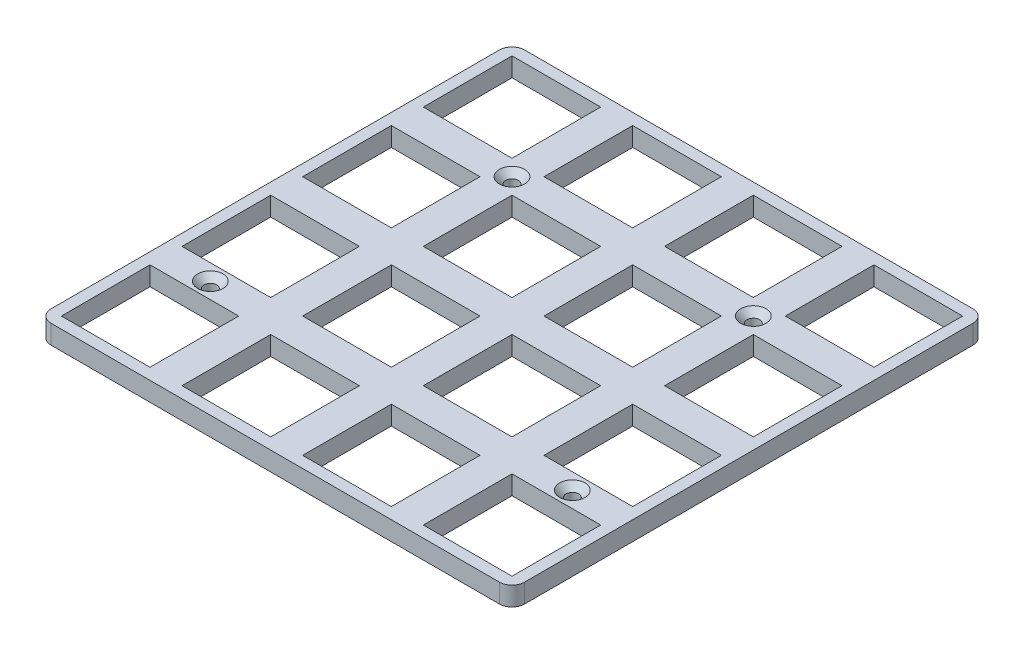
SolidWorks part; units mm, degrees
ref_plane "Front Plane" through (0, 0, 0) normal (0, 0, 1) x (1, 0, 0)
ref_plane "Top Plane" through (0, 0, 0) normal (0, 1, 0) x (1, 0, 0)
ref_plane "Right Plane" through (0, 0, 0) normal (1, 0, 0) x (0, 0, -1)
sketch "Sketch5" plane through (0, 0, 0) normal (1, 0, 0) x (0, 0, -1)
  line L0 (0, 0) -> (0, 13.4604) construction
sketch "Sketch1" plane through (0, 0, 0) normal (0, 1, 0) x (1, 0, 0)
  line L5 (-16.525, 21.575) -> (-16.525, 35.575)
  line L6 (-37.575, -37.575) -> (37.575, -37.575)
  line L11 (-37.575, -37.575) -> (-37.575, 37.575)
  line L12 (-37.575, 37.575) -> (37.575, 37.575)
  line L72 (37.575, -37.575) -> (37.575, 37.575)
  line L88 (-37.575, -37.575) -> (37.575, 37.575) construction
  line L89 (-37.575, 37.575) -> (37.575, -37.575) construction
  line L90 (-35.575, 21.575) -> (-21.575, 21.575)
  line L91 (-35.575, 21.575) -> (-35.575, 35.575)
  line L92 (-35.575, 35.575) -> (-21.575, 35.575)
  line L93 (-21.575, 21.575) -> (-21.575, 35.575)
  line L94 (-35.575, 21.575) -> (-21.575, 35.575) construction
  line L95 (-35.575, 35.575) -> (-21.575, 21.575) construction
  line L96 (-16.525, 21.575) -> (-2.525, 21.575)
  line L97 (-2.525, 21.575) -> (-2.525, 35.575)
  line L98 (-16.525, 35.575) -> (-2.525, 35.575)
  line L99 (2.525, 21.575) -> (2.525, 35.575)
  line L100 (2.525, 21.575) -> (16.525, 21.575)
  line L101 (16.525, 21.575) -> (16.525, 35.575)
  line L102 (2.525, 35.575) -> (16.525, 35.575)
  line L103 (21.575, 21.575) -> (21.575, 35.575)
  line L104 (21.575, 21.575) -> (35.575, 21.575)
  line L105 (35.575, 21.575) -> (35.575, 35.575)
  line L106 (21.575, 35.575) -> (35.575, 35.575)
  line L107 (-16.525, 2.525) -> (-16.525, 16.525)
  line L108 (-16.525, 2.525) -> (-2.525, 2.525)
  line L109 (-2.525, 2.525) -> (-2.525, 16.525)
  line L110 (-16.525, 16.525) -> (-2.525, 16.525)
  line L111 (2.525, 2.525) -> (2.525, 16.525)
  line L112 (2.525, 2.525) -> (16.525, 2.525)
  line L113 (16.525, 2.525) -> (16.525, 16.525)
  line L114 (2.525, 16.525) -> (16.525, 16.525)
  line L115 (21.575, 2.525) -> (21.575, 16.525)
  line L116 (21.575, 2.525) -> (35.575, 2.525)
  line L117 (35.575, 2.525) -> (35.575, 16.525)
  line L118 (21.575, 16.525) -> (35.575, 16.525)
  line L119 (-16.525, -16.525) -> (-16.525, -2.525)
  line L120 (-16.525, -16.525) -> (-2.525, -16.525)
  line L121 (-2.525, -16.525) -> (-2.525, -2.525)
  line L122 (-16.525, -2.525) -> (-2.525, -2.525)
  line L123 (2.525, -16.525) -> (2.525, -2.525)
  line L124 (2.525, -16.525) -> (16.525, -16.525)
  line L125 (16.525, -16.525) -> (16.525, -2.525)
  line L126 (2.525, -2.525) -> (16.525, -2.525)
  line L127 (21.575, -16.525) -> (21.575, -2.525)
  line L128 (21.575, -16.525) -> (35.575, -16.525)
  line L129 (35.575, -16.525) -> (35.575, -2.525)
  line L130 (21.575, -2.525) -> (35.575, -2.525)
  line L131 (-16.525, -35.575) -> (-16.525, -21.575)
  line L132 (-16.525, -35.575) -> (-2.525, -35.575)
  line L133 (-2.525, -35.575) -> (-2.525, -21.575)
  line L134 (-16.525, -21.575) -> (-2.525, -21.575)
  line L135 (2.525, -35.575) -> (2.525, -21.575)
  line L136 (2.525, -35.575) -> (16.525, -35.575)
  line L137 (16.525, -35.575) -> (16.525, -21.575)
  line L138 (2.525, -21.575) -> (16.525, -21.575)
  line L139 (21.575, -35.575) -> (21.575, -21.575)
  line L140 (21.575, -35.575) -> (35.575, -35.575)
  line L141 (35.575, -35.575) -> (35.575, -21.575)
  line L142 (21.575, -21.575) -> (35.575, -21.575)
  line L143 (-35.575, 2.525) -> (-35.575, 16.525)
  line L144 (-35.575, 2.525) -> (-21.575, 2.525)
  line L145 (-21.575, 2.525) -> (-21.575, 16.525)
  line L146 (-35.575, 16.525) -> (-21.575, 16.525)
  line L147 (-35.575, -16.525) -> (-35.575, -2.525)
  line L148 (-35.575, -16.525) -> (-21.575, -16.525)
  line L149 (-21.575, -16.525) -> (-21.575, -2.525)
  line L150 (-35.575, -2.525) -> (-21.575, -2.525)
  line L151 (-35.575, -35.575) -> (-35.575, -21.575)
  line L152 (-35.575, -35.575) -> (-21.575, -35.575)
  line L153 (-21.575, -35.575) -> (-21.575, -21.575)
  line L154 (-35.575, -21.575) -> (-21.575, -21.575)
  line L155 (-35.575, 21.575) -> (-16.525, 21.575) construction
  line L156 (-35.575, 21.575) -> (-35.575, 2.525) construction
  point P0 (0, 0)
  point P6 (-28.575, 28.575)
  dimension "D1" = 2
  dimension "D2" = 14
  dimension "D5" = 90
  dimension "D6" = 19.05
  dimension "D7" = 19.05
  dimension "D3" = 4
  dimension "D8" = 75.15
  dimension "D9" = 5.05
  dimension "D4" = 4
extrude "Boss-Extrude1" add sketch "Sketch1" along normal blind 3
sketch "Sketch2" plane through (0, 3, 0) normal (0, 1, 0) x (1, 0, 0)
  line L0 (-28.575, -16.525) -> (-28.575, -21.575) construction
  line L5 (-35.575, -16.525) -> (-21.575, -16.525) construction
  line L7 (-21.575, -21.575) -> (-35.575, -21.575) construction
  line L8 (-28.575, -19.05) -> (0, -19.05) construction
  line L9 (-21.575, 16.525) -> (-16.525, 16.525) construction
  line L10 (-21.575, 16.525) -> (-21.575, 21.575) construction
  line L11 (-21.575, 21.575) -> (-16.525, 21.575) construction
  line L12 (-16.525, 16.525) -> (-16.525, 21.575) construction
  line L15 (-21.575, 16.525) -> (-16.525, 21.575) construction
  line L20 (-21.575, 21.575) -> (-16.525, 16.525) construction
  line L22 (-19.05, 19.05) -> (0, 19.05) construction
  circle A0 centre (-19.05, 19.05) radius 1
  circle A1 centre (-28.575, -19.05) radius 1
  point P8 (-19.05, 19.05)
  point P17 (-28.575, -19.05)
  dimension "D1" = 2
  dimension "D2" = 2
  dimension "D3" = 19.05
  dimension "D4" = 28.575
extrude "Cut-Extrude1" cut sketch "Sketch2" against normal up to surface (3 mm away) up to face at (0, 0, 0)
sketch "Sketch3" plane through (0, 3, 0) normal (0, 1, 0) x (1, 0, 0)
  circle A2 centre (-19.05, 19.05) radius 2
  circle A3 centre (-19.05, 19.05) radius 2
  circle A4 centre (-28.575, -19.05) radius 2
  circle A5 centre (-28.575, -19.05) radius 2
  dimension "D1" = 1
  dimension "D2" = 1
extrude "Cut-Extrude2" [suppressed] cut sketch "Sketch3" against normal blind 1
chamfer "Chamfer1" distance 1 angle 45 2 edges at (-19.05, 3, -18.05) (-28.575, 3, 20.05)
mirror "Mirror1" about plane through (0, 0, 0) normal (1, 0, 0) of "Chamfer1", "Cut-Extrude1"
other "Move Face1" flip direction yes face at (37.575, 1.5, 0) face at (0, 1.5, -37.575) face at (0, 1.5, 37.575) face at (-37.575, 1.5, 0) offset 0.2 parameters "D1"=0.2
fillet "Fillet1" radius 2 4 edges at (-37.375, 1.5, -37.375) (37.375, 1.5, -37.375) (37.375, 1.5, 37.375) (-37.375, 1.5, 37.375)
equation "\"screwhole\"=2"
equation "\"D2@Sketch2\"=\"screwhole\""
equation "\"D1@Sketch2\"=\"screwhole\""
